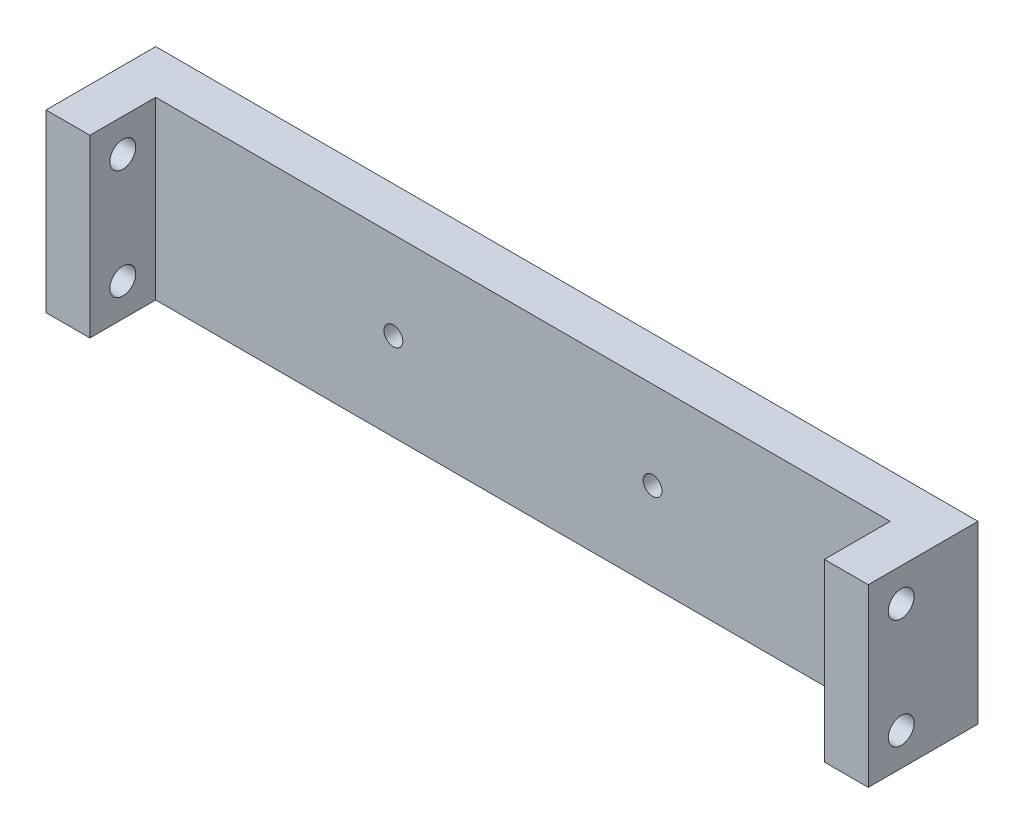
SolidWorks part; units mm, degrees
material "ABS"
ref_plane "Front Plane" through (0, 0, 0) normal (0, 0, 1) x (1, 0, 0)
ref_plane "Top Plane" through (0, 0, 0) normal (0, 1, 0) x (1, 0, 0)
ref_plane "Right Plane" through (0, 0, 0) normal (1, 0, 0) x (0, 0, -1)
sketch "Sketch1" plane through (0, 0, 0) normal (0, 0, 1) x (1, 0, 0)
  line L0 (90.0938, 20.32) -> (90.0938, 0)
  line L1 (0, 0) -> (95.1738, 0)
  line L2 (0, 0) -> (0, 20.32)
  line L3 (0, 20.32) -> (95.1738, 20.32)
  line L4 (95.1738, 0) -> (95.1738, 20.32)
  line L5 (5.08, 20.32) -> (5.08, 0)
  line L6 (5.08, 10.16) -> (90.0938, 10.16) construction
  circle A0 centre (32.5869, 10.16) radius 1.0922
  circle A1 centre (62.5869, 10.16) radius 1.0922
  point P15 (47.5869, 10.16)
  dimension "D3" = 30
  dimension "D6" = 2.1844
  dimension "D1" = 5.08
  dimension "D2" = 5.08
  dimension "D4" = 95.1738
  dimension "D5" = 15
  dimension "D7" = 20.32
extrude "Boss-Extrude1" add sketch "Sketch1" along normal blind 5.08 contours L5 L6 A0 A1 L0 L3 | L6 L5 L1 L0 A1 A0 region at (47.5869, 15.2601, 0) region at (47.5869, 5.0599, 0)
extrude "Boss-Extrude2" add sketch "Sketch1<3>" along normal blind 12.7 contours L1 L4 L3 L0 | L5 L3 L2 L1 region at (92.6338, 10.16, 0) region at (2.54, 10.16, 0)
sketch "Sketch1<3>" plane through (0, 0, 0) normal (0, 0, 1) x (1, 0, 0) same geometry as "Sketch1"
sketch "Sketch2" plane through (90.0938, 0, 0) normal (-1, 0, 0) x (0, 0, 1)
  line L0 (8.89, 20.32) -> (8.89, 0) construction
  line L1 (12.7, 20.32) -> (5.08, 20.32) construction
  line L2 (12.7, 0) -> (5.08, 0) construction
  circle A0 centre (8.89, 16.51) radius 1.5
  circle A1 centre (8.89, 3.81) radius 1.5
  point P12 (8.89, 10.16)
  dimension "D1" = 12.7
  dimension "D2" = 6.35
  dimension "D3" = 3
extrude "Cut-Extrude1" cut sketch "Sketch2" along normal through all both and the other way through all
